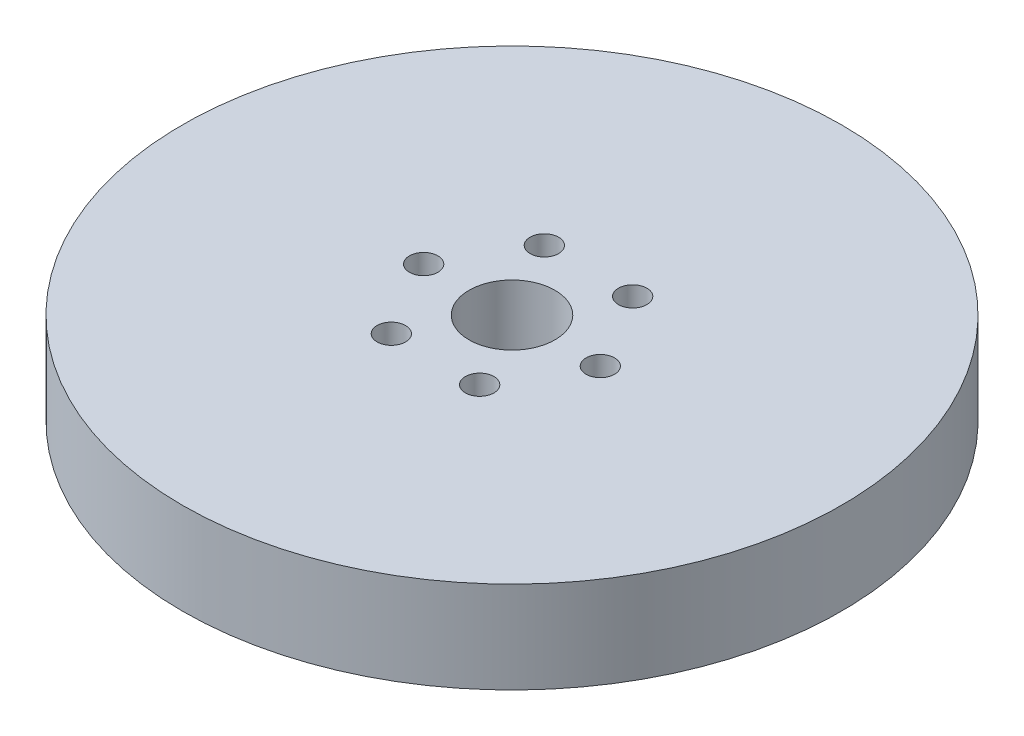
SolidWorks part; units mm, degrees
ref_plane "Front Plane" through (0, 0, 0) normal (0, 0, 1) x (1, 0, 0)
ref_plane "Top Plane" through (0, 0, 0) normal (0, 1, 0) x (1, 0, 0)
ref_plane "Right Plane" through (0, 0, 0) normal (1, 0, 0) x (0, 0, -1)
sketch "Sketch1" plane through (0, 0, 0) normal (0, 1, 0) x (1, 0, 0)
  circle A0 centre (0, 0) radius 57.5
  dimension "FLANGE_OD" = 115
extrude "Boss-Extrude1" add sketch "Sketch1" along normal blind 16
sketch "Sketch2" plane through (0, 0, 0) normal (0, 1, 0) x (1, 0, 0)
  circle A0 centre (0, 0) radius 7.5
  dimension "BORE_D" = 15
extrude "Cut-Extrude1" cut sketch "Sketch2" along normal through all
sketch "Sketch3" plane through (0, 16, 0) normal (0, 1, 0) x (1, 0, 0)
  circle A0 centre (0, 0) radius 15.412 construction
  circle A1 centre (-15.412, 0) radius 2.4871
  dimension "BOLT_D" = 4.9741
  dimension "BOLT_PCD" = 30.824
extrude "Cut-Extrude2" cut sketch "Sketch3" against normal blind 13.7615
pattern_circular "CirPattern1" count 6 over 360 about axis through (0, 0, 0) along (0, 1, 0) of "Cut-Extrude2"
